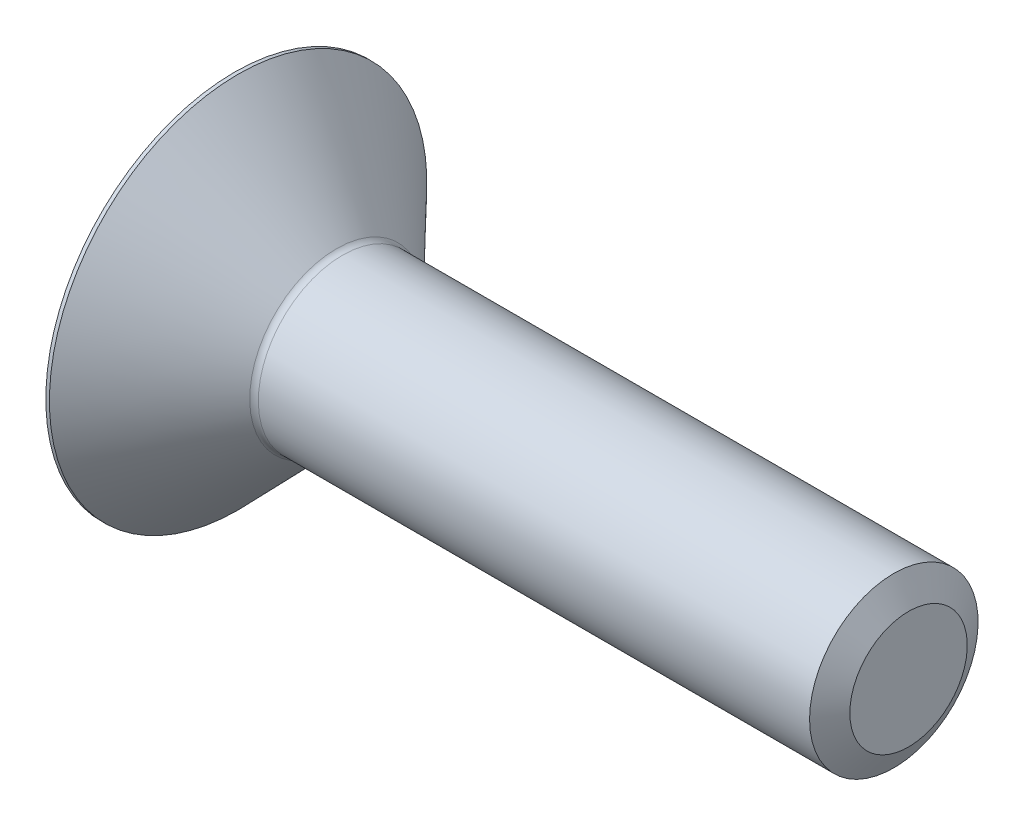
SolidWorks part; units mm, degrees
ref_plane "前视基准面" through (0, 0, 0) normal (0, 0, 1) x (1, 0, 0)
ref_plane "上视基准面" through (0, 0, 0) normal (0, 1, 0) x (1, 0, 0)
ref_plane "右视基准面" through (0, 0, 0) normal (1, 0, 0) x (0, 0, -1)
sketch "草图1" plane through (0, 0, 0) normal (0, 0, 1) x (1, 0, 0)
  line L0 (0, 2) -> (-13.4351, 2)
  line L1 (-13.579, 2.0611) -> (-15.9149, 4.48)
  line L2 (-15.9149, 4.48) -> (-16, 4.48)
  line L3 (-16, 4.48) -> (-16, 0)
  line L4 (-16, 0) -> (0, 0)
  line L5 (0, 0) -> (0, 2)
  line L6 (0, 0) -> (-16, 0) construction
  arc A0 (-13.4351, 2) -> (-13.579, 2.0611) centre (-13.4351, 2.2) cw
  point P9 (-13.52, 2)
  dimension "r" = 0.2
  dimension "k" = 2.48
  dimension "dk" = 8.96
  dimension "l" = 16
  dimension "d" = 4
  dimension "D5" = 46
revolve "旋转1" add sketch "草图1" angle 360 about L6
cosmetic thread "装饰螺纹线1" parameters "b"=10, "D2"=3.44
sketch "草图2" plane through (-16, 0, 0) normal (-1, 0, 0) x (0, 0, 1)
  line L1 (0, 1.4434) -> (-1.25, 0.7217)
  line L2 (-1.25, 0.7217) -> (-1.25, -0.7217)
  line L3 (-1.25, -0.7217) -> (0, -1.4434)
  line L4 (0, -1.4434) -> (1.25, -0.7217)
  line L5 (1.25, -0.7217) -> (1.25, 0.7217)
  line L6 (1.25, 0.7217) -> (0, 1.4434)
  circle A0 centre (0, 0) radius 1.25 construction
  dimension "s" = 2.5
extrude "切除-拉伸1" cut sketch "草图2" against normal blind 2.58
sketch "草图6" plane through (0, 0, 0) normal (0, 0, 1) x (1, 0, 0)
  line L0 (-14.5, 1.4434) -> (-13.6667, 0)
  line L1 (-13.6667, 0) -> (-13.05, 0)
  line L2 (-13.05, 0) -> (-13.05, 1.4434)
  line L3 (-13.05, 1.4434) -> (-14.5, 1.4434)
  line L4 (-16, 0) -> (-13.42, 0) construction
  line L5 (-16, 0) -> (-18.87, 0) construction
  dimension "t" = 1.5
  dimension "D1" = 60
  dimension "t1" = 2.58
  dimension "e-s" = 0.37
  dimension "e" = 2.87
revolve "旋转2" add sketch "草图6" angle 360 about L4
sketch "草图7" plane through (0, 0, 0) normal (0, 0, 1) x (1, 0, 0)
  line L0 (-16, 1.4434) -> (-16, 0)
  line L1 (-16, 0) -> (-15.593, 0)
  line L2 (-15.593, 0) -> (-16, 1.4434)
  line L3 (-16, 0) -> (-15.593, 0) construction
  dimension "e-s*1.1" = 0.407
revolve "切除-旋转2" cut sketch "草图7" angle 360 about L3
sketch "草图4" plane through (0, 0, 0) normal (0, 0, 1) x (1, 0, 0)
  line L0 (-0.35, 2) -> (0, 1.3938)
  line L1 (0, -2) -> (0, 2) construction
  line L2 (0, 1.3938) -> (0.35, 2)
  line L3 (0.35, 2) -> (-0.35, 2)
  line L4 (-0.35, 0) -> (0.35, 0) construction
  dimension "d" = 4
  dimension "p" = 0.7
revolve "切除-旋转1" cut sketch "草图4" angle 360 about L4
ref_axis "基准轴1" through (-21.1715, 0, 0) along (1, 0, 0)
pattern_linear "阵列(线性)2" [suppressed] count 14 spacing 0.7 along (-1, 0, 0) of bodies 104
equation "\"D2@装饰螺纹线1\" = \"d@草图1\" * 0.86"
equation "\"e-s@草图6\" = \"e@草图6\" - \"s@草图2\""
equation "\"t1@切除-拉伸1\" = \"k@草图1\" + 0.1"
equation "\"t1@草图6\" = \"t1@切除-拉伸1\""
equation "\"e-s*1.1@草图7\" = \"e-s@草图6\" * 1.1"
equation "\"d@草图4\" = \"d@草图1\""
equation "\"D3@阵列(线性)2\" = \"p@草图4\""
equation "\"D1@阵列(线性)2\" = \"b@装饰螺纹线1\" / \"p@草图4\""
